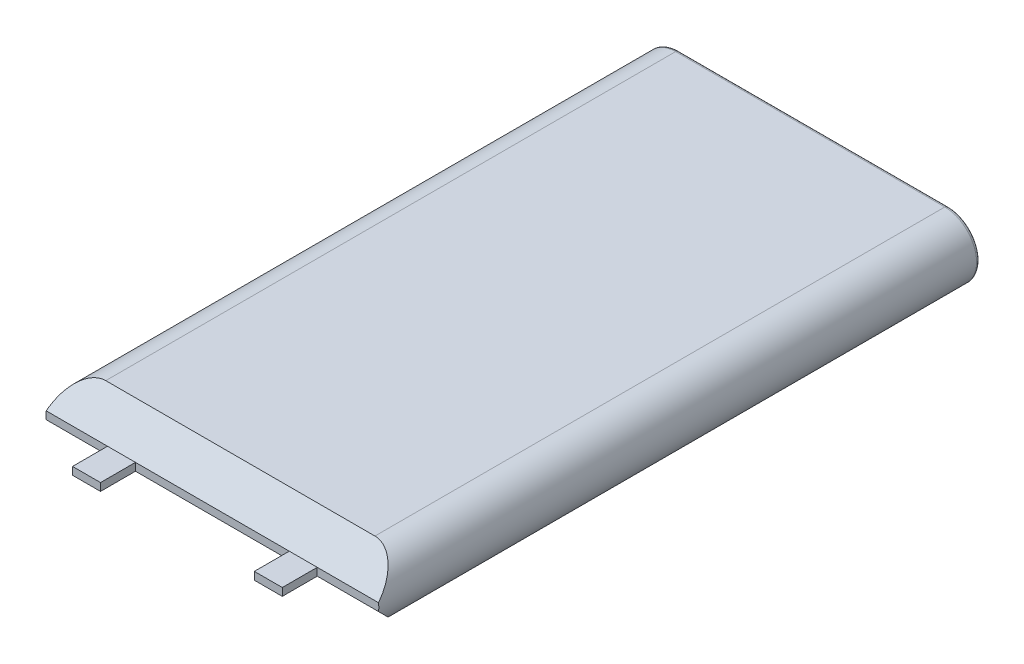
SolidWorks part; units mm, degrees
ref_plane "Front Plane" through (0, 0, 0) normal (0, 0, 1) x (1, 0, 0)
ref_plane "Top Plane" through (0, 0, 0) normal (0, 1, 0) x (1, 0, 0)
ref_plane "Right Plane" through (0, 0, 0) normal (1, 0, 0) x (0, 0, -1)
sketch "Sketch1" plane through (0, 0, 0) normal (0, 0, 1) x (1, 0, 0)
  line L1 (24.4475, -5.7785) -> (-24.4475, -5.7785)
  line L2 (24.4475, -5.7785) -> (24.4475, 5.7785) construction
  line L3 (24.4475, 5.7785) -> (-24.4475, 5.7785)
  line L4 (-24.4475, -5.7785) -> (-24.4475, 5.7785) construction
  line L5 (24.4475, -5.7785) -> (-24.4475, 5.7785) construction
  line L6 (24.4475, 5.7785) -> (-24.4475, -5.7785) construction
  arc A0 (-24.4475, 5.7785) -> (-24.4475, -5.7785) centre (-24.4475, 0) ccw
  arc A1 (24.4475, -5.7785) -> (24.4475, 5.7785) centre (24.4475, 0) ccw
  point P0 (0, 0)
  point P7 (-30.226, 0)
  point P9 (30.226, 0)
  dimension "D1" = 60.452
  dimension "D2" = 11.557
extrude "Boss-Extrude1" add sketch "Sketch1" along normal blind 109.22
fillet "Fillet1" radius 0.635 4 edges at (0, -5.7785, 0) (30.226, 0, 0) (0, 5.7785, 0) (-30.226, 0, 0)
chamfer "Chamfer1" distance 5.08 angle 45 2 edges at (0, -5.7785, 109.22) (0, 5.7785, 109.22) tangent propagation no
sketch "Sketch2" plane through (0, 0, 109.22) normal (0, 0, 1) x (1, 0, 0)
  line L0 (30.1836, 0.6985) -> (-30.1836, 0.6985) construction
  line L1 (-19.05, 0.6985) -> (-13.97, 0.6985)
  line L2 (-19.05, 0.6985) -> (-19.05, -0.6985)
  line L3 (-19.05, -0.6985) -> (-13.97, -0.6985)
  line L4 (-13.97, 0.6985) -> (-13.97, -0.6985)
  line L5 (-30.1836, -0.6985) -> (30.1836, -0.6985) construction
  line L6 (0, 0.6985) -> (0, -0.6985) construction
  line L7 (19.05, -0.6985) -> (13.97, -0.6985)
  line L8 (13.97, 0.6985) -> (13.97, -0.6985)
  line L9 (19.05, 0.6985) -> (13.97, 0.6985)
  line L10 (19.05, 0.6985) -> (19.05, -0.6985)
  dimension "D1" = 5.08
  dimension "D2" = 38.1
extrude "Boss-Extrude2" add sketch "Sketch2" along normal blind 6.35
